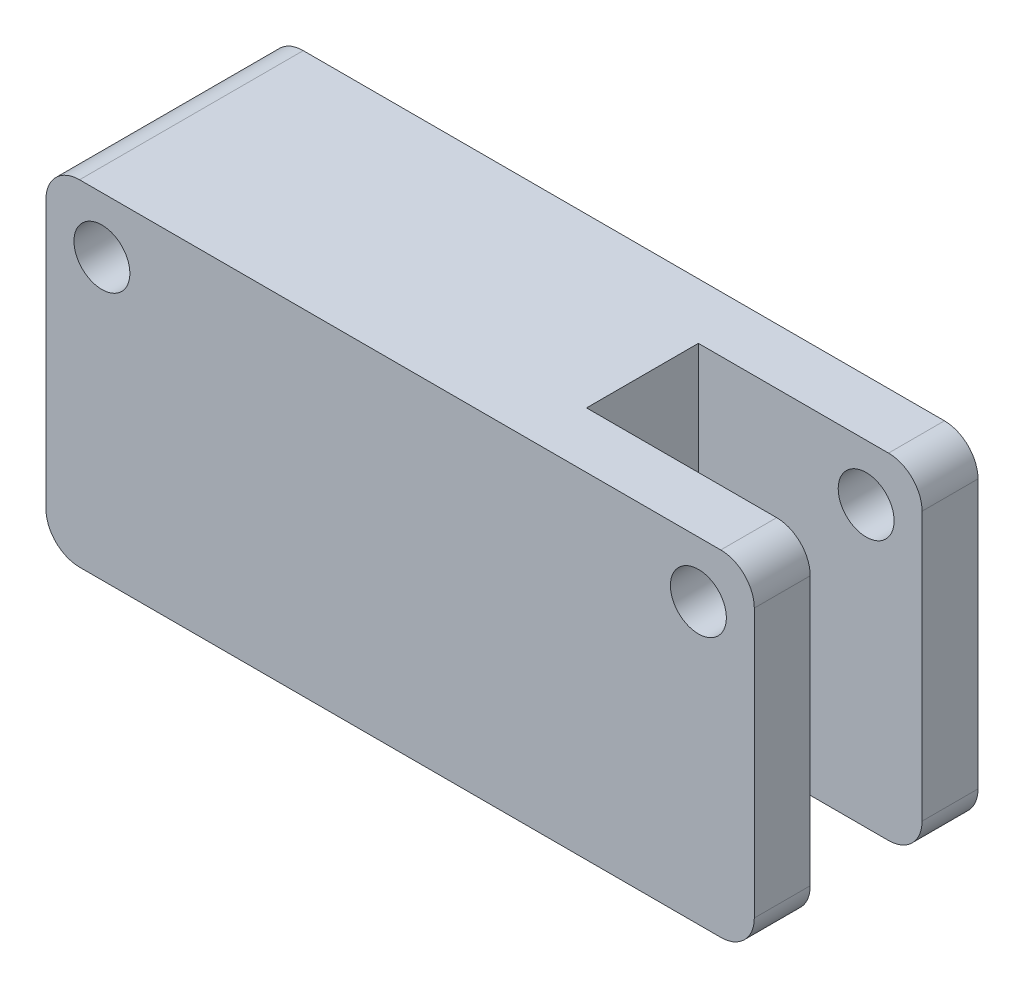
SolidWorks part; units mm, degrees
ref_plane "Plan de face" through (0, 0, 0) normal (0, 0, 1) x (1, 0, 0)
ref_plane "Plan de dessus" through (0, 0, 0) normal (0, 1, 0) x (1, 0, 0)
ref_plane "Plan de droite" through (0, 0, 0) normal (1, 0, 0) x (0, 0, -1)
sketch "Esquisse2" plane through (0, 0, 0) normal (0, 1, 0) x (1, 0, 0)
  line L0 (0, 0) -> (56.0293, 0) construction
  line L1 (0, -10) -> (63.33, -10)
  line L2 (0, -10) -> (0, 10)
  line L3 (0, 10) -> (63.33, 10)
  line L4 (63.33, -10) -> (63.33, 10)
  line L5 (0, 0) -> (0, -42.7765) construction
  dimension "D1" = 63.33
extrude "Boss.-Extru.1" add sketch "Esquisse2" along normal mid plane 30
fillet "Congé1" radius 3 4 edges at (0, 15, 0) (63.33, 15, 0) (63.33, -15, 0) (0, -15, 0)
sketch "Esquisse4" plane through (0, 15, 0) normal (0, 1, 0) x (1, 0, 0)
  line L0 (63.33, 10) -> (63.33, -10) construction
  line L1 (63.33, 5) -> (63.33, -5)
  line L2 (63.33, -5) -> (43.33, -5)
  line L4 (43.33, -5) -> (43.33, 5)
  line L6 (43.33, 5) -> (63.33, 5)
  line L7 (3, -10) -> (60.33, -10) construction
  line L8 (63.6485, 0) -> (81.8664, 0) construction
  dimension "D1" = 20
  dimension "D2" = 5
extrude "Enlèv. mat.-Extru.1" cut sketch "Esquisse4" against normal through all
sketch "Esquisse5" plane through (0, 0, -10) normal (0, 0, -1) x (-1, 0, 0)
  line L0 (-60.33, 15) -> (-3, 15) construction
  line L1 (-63.33, 12) -> (-63.33, -12) construction
  line L2 (-31.665, 0) -> (-31.665, 9.0949) construction
  circle A0 centre (-58.33, 10) radius 2.5
  circle A1 centre (-5, 10) radius 2.5
  dimension "D1" = 5
  dimension "D2" = 5
  dimension "D3" = 5
  dimension "D4" = 31.665
extrude "Enlèv. mat.-Extru.2" cut sketch "Esquisse5" against normal through all
ref_axis "Axe1" through (5, 10, 10) along (0, 0, -1)
ref_point "Point1"
equation "\"L\"= 0.02m"
equation "\"ldoigt\"= 0.06333m"
equation "\"D1@Esquisse2\"=\"ldoigt\""
equation "\"D2@Esquisse2\"=\"L\""
equation "\"e\"= 0.03m"
equation "\"D1@Congé1\"=\"e\"/10m"
equation "\"D4@Esquisse5\"=\"ldoigt\"/2"
